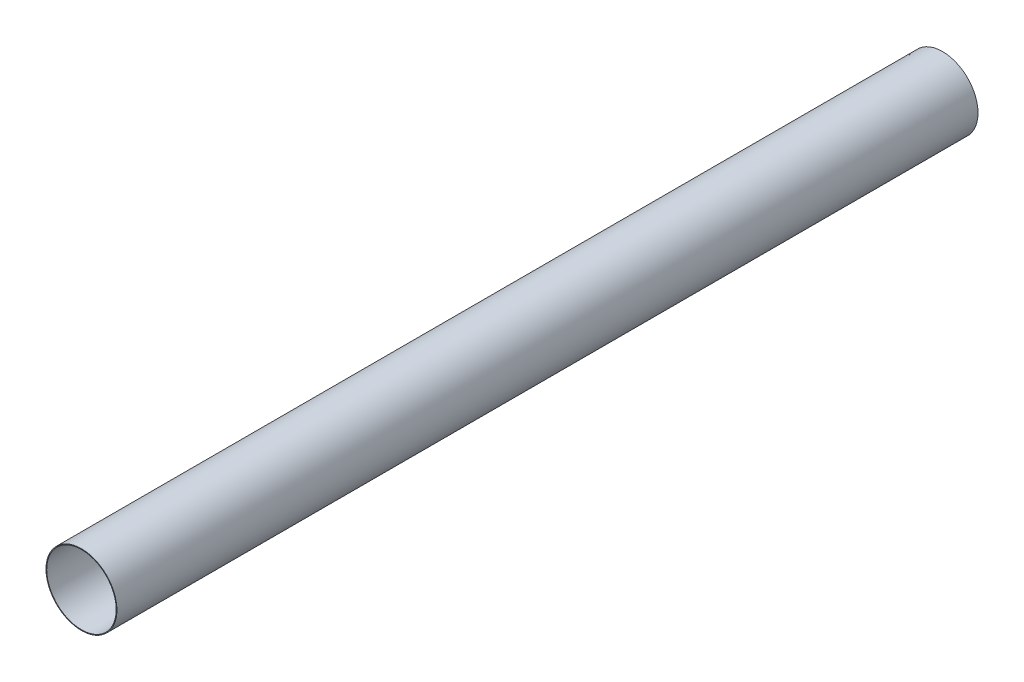
SolidWorks part; units mm, degrees
material "Thornel VCB-20 Carbon Cloth"
ref_plane "Front Plane" through (0, 0, 0) normal (0, 0, 1) x (1, 0, 0)
ref_plane "Top Plane" through (0, 0, 0) normal (0, 1, 0) x (1, 0, 0)
ref_plane "Right Plane" through (0, 0, 0) normal (1, 0, 0) x (0, 0, -1)
sketch "Sketch1" plane through (0, 0, 0) normal (0, 0, 1) x (1, 0, 0)
  circle A0 centre (0, 0) radius 73.5
  circle A1 centre (0, 0) radius 75
  dimension "D1" = 150
  dimension "D2" = 1.5
extrude "Boss-Extrude1" add sketch "Sketch1" along normal up to surface (1821.2047 mm away)
